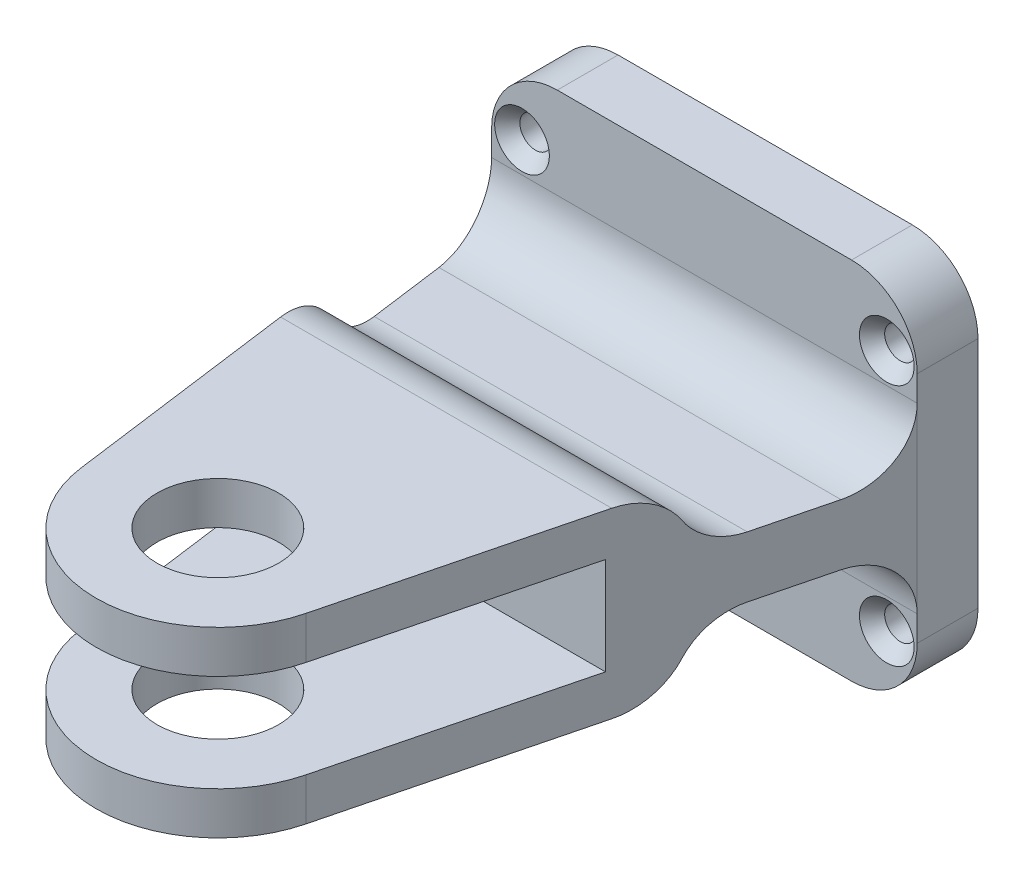
SolidWorks part; units mm, degrees
material "6061-T6 (SS)"
ref_plane "XY" through (0, 0, 0) normal (0, 0, 1) x (1, 0, 0)
ref_plane "XZ" through (0, 0, 0) normal (0, 1, 0) x (1, 0, 0)
ref_plane "YZ" through (0, 0, 0) normal (1, 0, 0) x (0, 0, -1)
ref_axis "X" through (-24.4475, 0, 0) along (1, 0, 0)
ref_axis "Y" through (0, -20.955, 0) along (0, 1, 0)
ref_axis "Z" through (0, 0, 66.8777) along (0, 0, -1)
sketch "Sketch1" plane through (0, 0, 0) normal (0, 0, 1) x (1, 0, 0)
  line L1 (-22.225, -19.05) -> (22.225, -19.05)
  line L2 (-22.225, -19.05) -> (-22.225, 19.05)
  line L3 (-22.225, 19.05) -> (22.225, 19.05)
  line L4 (22.225, -19.05) -> (22.225, 19.05)
  line L5 (-22.225, -19.05) -> (22.225, 19.05) construction
  line L6 (-22.225, 19.05) -> (22.225, -19.05) construction
  point P0 (0, 0)
  dimension "D1" = 38.1
  dimension "D2" = 44.45
extrude "Boss-Extrude1" add sketch "Sketch1" along normal blind 6.35
hole_wizard "CSK for #4 Flat Head Machine Screw1" positions "Sketch2" profile "Sketch3" countersink size "#4" standard "ANSI Inch" end condition up to next
sketch "Sketch2" plane through (0, 0, 6.35) normal (0, 0, 1) x (1, 0, 0)
  line L1 (-19.05, 12.7) -> (19.05, 12.7)
  line L2 (-19.05, 12.7) -> (-19.05, -12.7)
  line L3 (-19.05, -12.7) -> (19.05, -12.7)
  line L4 (19.05, 12.7) -> (19.05, -12.7)
  line L5 (0, -12.7) -> (0, 12.7) construction
  point P0 (-19.05, 12.7)
  point P5 (19.05, -12.7)
  point P108 (-19.05, -12.7)
  point P109 (19.05, 12.7)
  dimension "D1" = 25.4
  dimension "D2" = 38.1
sketch "Sketch3" plane through (-19.05, 12.7, 6.35) normal (1, 0, 0) x (0, -1, 0)
  line L0 (0, 0) -> (0, 6.35)
  line L1 (0, 6.35) -> (1.6319, 6.35)
  line L2 (1.6319, 6.35) -> (1.6319, 1.4098)
  line L3 (1.6319, 1.4098) -> (2.8575, 0)
  line L5 (2.8575, 0) -> (0, 0)
  line L6 (-1.6319, 1.4098) -> (-2.8575, 0) construction
  line L11 (0, -6.35) -> (0, 107.95) construction
  dimension "Thru Hole Dia." = 3.2639
  dimension "Thru Hole Depth" = 6.35
  dimension "Near C'Sink Dia." = 5.715
  dimension "Near C'Sink Angle" = 82
sketch "Sketch4" plane through (0, 0, 0) normal (0, 1, 0) x (1, 0, 0)
  line L0 (0, 0) -> (-3, -54.168) construction
  line L1 (-15.5874, -55.8557) -> (-22.225, -6.35)
  line L2 (-22.225, -6.35) -> (22.225, -6.35) construction
  line L3 (9.3105, -57.2891) -> (22.225, -6.35)
  line L4 (-22.225, -6.35) -> (22.225, -6.35)
  line L5 (22.225, 0) -> (-22.225, 0) construction
  circle A0 centre (-3, -54.168) radius 12.7 construction
  circle A1 centre (-3, -54.168) radius 6.35
  arc A2 (-15.5874, -55.8557) -> (9.3105, -57.2891) centre (-3, -54.168) ccw
  dimension "D1" = 25.4
  dimension "D3" = 12.7
  dimension "D4" = 25.4
  dimension "D2" = 54.168
  dimension "D5" = 3
extrude "Boss-Extrude2" add sketch "Sketch4" along normal mid plane 6.35
sketch "Sketch5" plane through (0, 0, 0) normal (0, 1, 0) x (1, 0, 0)
  line L0 (17.0244, -26.863) -> (-19.4747, -26.863)
  line L3 (9.3105, -57.2891) -> (22.225, -6.35)
  line L4 (22.225, -6.35) -> (-22.225, -6.35)
  line L5 (-22.225, -6.35) -> (-15.5874, -55.8557)
  line L6 (9.3105, -57.2891) -> (17.0244, -26.863)
  line L8 (-19.4747, -26.863) -> (-15.5874, -55.8557)
  circle A0 centre (-3, -54.168) radius 6.35 construction
  arc A1 (-15.5874, -55.8557) -> (9.3105, -57.2891) centre (-3, -54.168) ccw
  arc A2 (-15.5874, -55.8557) -> (9.3105, -57.2891) centre (-3, -54.168) ccw
  circle A3 centre (-3, -54.168) radius 6.35
  point P7 (-19.0078, -30.3447)
  dimension "D2" = 27.305
  dimension "D1" = 0
extrude "Boss-Extrude3" add sketch "Sketch5" along normal mid plane 19.05
sketch "Sketch6" plane through (0, 0, 0) normal (0, 1, 0) x (1, 0, 0)
  line L0 (-18.7425, -32.324) -> (15.6399, -32.324)
  line L3 (-19.4747, -26.863) -> (-15.5874, -55.8557)
  line L4 (17.0244, -26.863) -> (-19.4747, -26.863)
  line L5 (9.3105, -57.2891) -> (17.0244, -26.863)
  line L6 (-18.7425, -32.324) -> (-15.5874, -55.8557)
  line L8 (9.3105, -57.2891) -> (15.6399, -32.324)
  arc A1 (-15.5874, -55.8557) -> (9.3105, -57.2891) centre (-3, -54.168) ccw
  arc A2 (-15.5874, -55.8557) -> (9.3105, -57.2891) centre (-3, -54.168) ccw
  dimension "D2" = 21.844
  dimension "D1" = 0
extrude "Cut-Extrude1" cut sketch "Sketch6" against normal mid plane 10.16
fillet "Fillet3" radius 6.35 4 edges at (0, 3.175, 6.35) (0, -3.175, 6.35) (-1.2251, -3.175, 26.863) (-1.2251, 3.175, 26.863)
fillet "Fillet2" radius 6.858 6 edges at (-22.225, 19.05, 3.175) (-22.225, -19.05, 3.175) (22.225, -19.05, 3.175) (22.225, 19.05, 3.175) (-1.2251, 9.525, 26.863) (-1.2251, -9.525, 26.863)
